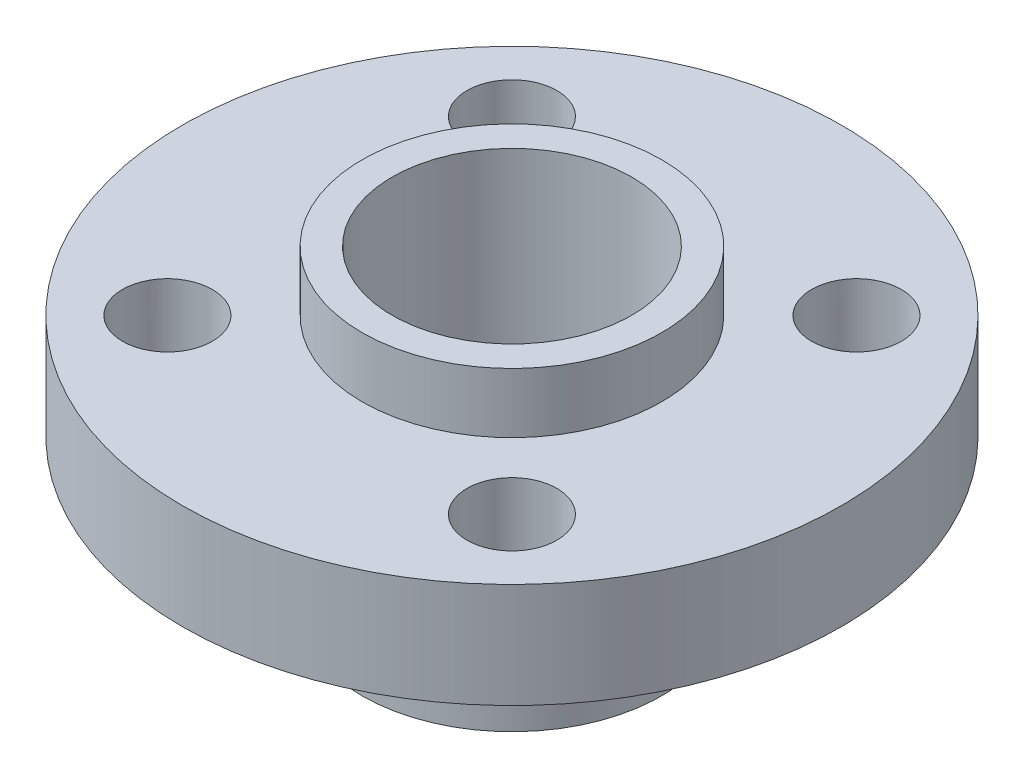
SolidWorks part; units mm, degrees
ref_plane "Front Plane" through (0, 0, 0) normal (0, 0, 1) x (1, 0, 0)
ref_plane "Top Plane" through (0, 0, 0) normal (0, 1, 0) x (1, 0, 0)
ref_plane "Right Plane" through (0, 0, 0) normal (1, 0, 0) x (0, 0, -1)
sketch "Sketch1" plane through (0, 0, 0) normal (0, 1, 0) x (1, 0, 0)
  circle A0 centre (0, 0) radius 4
  circle A1 centre (0, 0) radius 5
  dimension "D1" = 8
  dimension "D2" = 10
extrude "Boss-Extrude1" add sketch "Sketch1" along normal blind 10.5
sketch "Sketch2" plane through (0, 10.5, 0) normal (0, 1, 0) x (1, 0, 0)
  circle A0 centre (0, 0) radius 4.5
  circle A1 centre (0, 0) radius 11
  dimension "D1" = 9
  dimension "D2" = 22
extrude "Boss-Extrude2" add sketch "Sketch2" against normal blind 3.5 from offset 2 offset against normal yes
sketch "Sketch3" plane through (0, 8.5, 0) normal (0, 1, 0) x (1, 0, 0)
  line L0 (0, 0) -> (0, 11) construction
  line L1 (0, 0) -> (11, 0) construction
  line L2 (0, 0) -> (-7.7782, 7.7782) construction
  line L3 (0, 0) -> (7.7782, 7.7782) construction
  line L4 (0, 0) -> (7.7782, -7.7782) construction
  line L5 (0, 0) -> (-7.7782, -7.7782) construction
  circle A0 centre (0, 0) radius 11 construction
  circle A1 centre (-5.75, 5.75) radius 1.5
  circle A2 centre (5.75, 5.75) radius 1.5
  circle A3 centre (5.75, -5.75) radius 1.5
  circle A4 centre (-5.75, -5.75) radius 1.5
  dimension "D1" = 45
  dimension "D3" = 3
  dimension "D2" = 5.75
extrude "Cut-Extrude1" cut sketch "Sketch3" against normal through all
